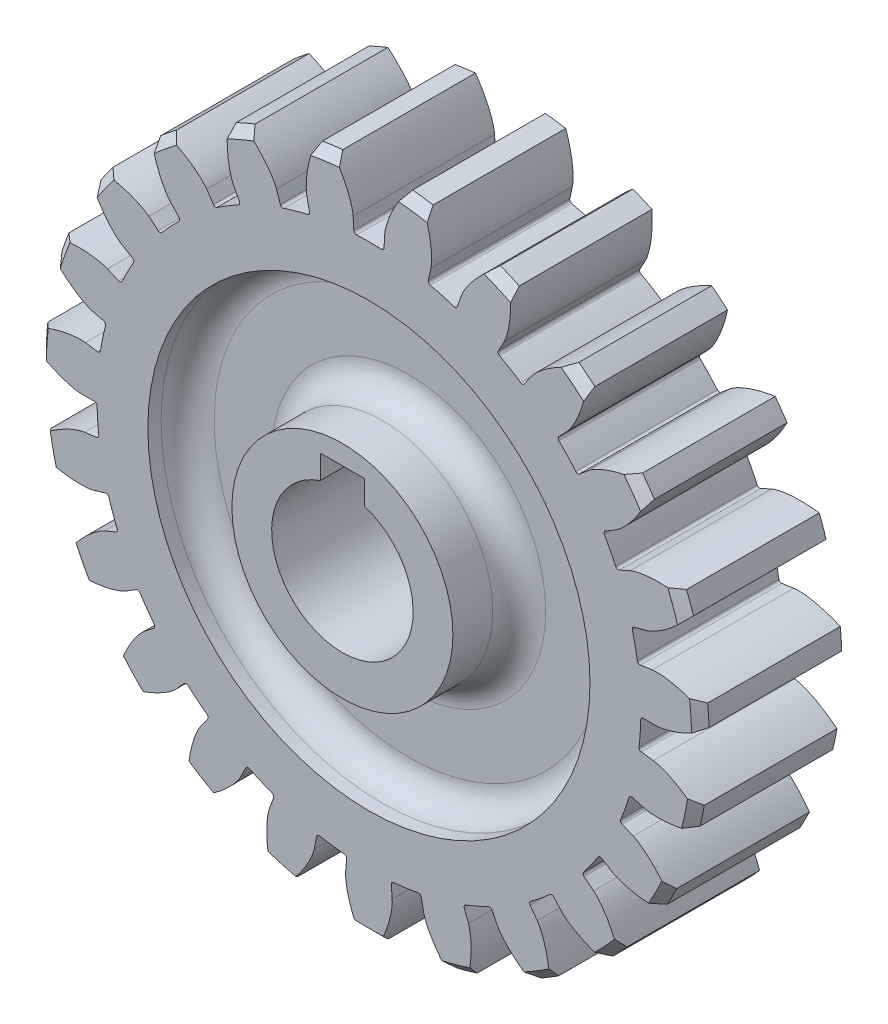
SolidWorks part; units mm, degrees
ref_plane "中间平面" through (0, 0, 0) normal (0, 0, 1) x (1, 0, 0)
ref_plane "上视基准面" through (0, 0, 0) normal (0, 1, 0) x (1, 0, 0)
ref_plane "右视基准面" through (0, 0, 0) normal (1, 0, 0) x (0, 0, -1)
sketch "直齿轮" plane through (0, 0, 0) normal (0, 0, 1) x (1, 0, 0)
  line L0 (0, 0) -> (-2.3544, 34.4196) construction
  line L2 (-1.787, 32.3701) -> (0, 0)
  line L3 (0, 0) -> (0, 52) construction
  line L4 (2.3544, 34.4196) -> (0, 0) construction
  line L6 (0, 0) -> (1.787, 32.3701)
  circle A0 centre (0, 0) radius 32.4194
  circle A1 centre (0, 0) radius 30.75
  arc A2 (2.3544, 34.4196) -> (-2.3544, 34.4196) centre (0, 0) ccw
  circle A3 centre (0, 0) radius 37.5
  spline S0 degree 4 poles (-1.787, 32.3701) (-1.7887, 32.4009) (-1.7934, 32.4623) (-1.8081, 32.5848) (-1.8484, 32.8281) (-1.9198, 33.1474) (-2.0304, 33.5397) (-2.2127, 34.0782) (-2.4377, 34.6365) (-2.7111, 35.2233) (-3.1079, 35.9742) (-3.8554, 37.2208) (-5.1552, 38.9723) (-7.4145, 41.3347) (-10.7378, 43.9018) (-14.7558, 46.1681) (-19.3803, 47.9889) (-24.1918, 49.2236) (-29.1102, 49.907) (-34.3171, 50.0805) (-40.7527, 49.6222) (-48.3054, 48.0952) (-56.7314, 45.058) (-64.3662, 40.876) (-70.4218, 36.5402) (-76.0488, 31.6736) (-80.363, 27.2133) (-84.2805, 22.4024) (-87.7873, 17.291) (-90.3418, 13.0408) (-93.2175, 7.5498) (-96.156, 0.7112) (-98.2587, -5.7849) (-99.6885, -11.8176) (-100.4666, -16.0841) (-100.8478, -18.5329) (-101.166, -20.9904) (-101.3894, -23.1477) (-101.5419, -24.9995) (-101.6431, -26.5457) (-101.7087, -27.7814) (-101.7587, -29.0225) (-101.7936, -30.2555) (-101.811, -31.3931) (-101.8163, -32.3958) (-101.8115, -33.3287) (-101.803, -34.0741) (-101.7825, -35.0407) (-101.7621, -35.7456) (-101.7112, -37.1392) (-101.6516, -38.2432) (-101.5692, -39.582) (-101.4747, -40.777) (-101.3876, -41.8018) (-101.2922, -42.7795) (-101.1864, -43.7836) (-101.0428, -45.0197) (-100.8513, -46.5113) (-100.6365, -47.9927) (-100.3982, -49.4757) (-100.227, -50.4595) (-100.1383, -50.9523) (-100.0932, -51.1978) knots 0 0 0 0 0 0.000701 0.001401 0.002802 0.005604 0.008133 0.010661 0.015718 0.019279 0.022839 0.02996 0.048734 0.068727 0.096889 0.125051 0.153212 0.181374 0.209535 0.237696 0.271429 0.327752 0.384075 0.440398 0.46856 0.496721 0.553044 0.581206 0.609367 0.637529 0.66569 0.722013 0.778336 0.792417 0.806497 0.820578 0.834659 0.84874 0.85578 0.86282 0.869861 0.876901 0.883942 0.890982 0.895509 0.900036 0.904564 0.909091 0.914773 0.920455 0.931818 0.9375 0.943182 0.948864 0.954545 0.960227 0.965909 0.977273 0.988636 0.994318 1 1 1 1 1 construction
  spline S1 degree 4 poles (-1.787, 32.3701) (-1.7887, 32.4009) (-1.7934, 32.4623) (-1.8081, 32.5848) (-1.8484, 32.8281) (-1.9198, 33.1474) (-2.0304, 33.5397) (-2.2127, 34.0782) (-2.4377, 34.6365) (-2.7111, 35.2233) (-3.1079, 35.9742) (-3.8554, 37.2208) (-5.1552, 38.9723) (-7.4145, 41.3347) (-10.7378, 43.9018) (-14.7558, 46.1681) (-19.3803, 47.9889) (-24.1918, 49.2236) (-29.1102, 49.907) (-34.3171, 50.0805) (-40.7527, 49.6222) (-48.3054, 48.0952) (-56.7314, 45.058) (-64.3662, 40.876) (-70.4218, 36.5402) (-76.0488, 31.6736) (-80.363, 27.2133) (-84.2805, 22.4024) (-87.7873, 17.291) (-90.3418, 13.0408) (-93.2175, 7.5498) (-96.156, 0.7112) (-98.2587, -5.7849) (-99.6885, -11.8176) (-100.4666, -16.0841) (-100.8478, -18.5329) (-101.166, -20.9904) (-101.3894, -23.1477) (-101.5419, -24.9995) (-101.6431, -26.5457) (-101.7087, -27.7814) (-101.7587, -29.0225) (-101.7936, -30.2555) (-101.811, -31.3931) (-101.8163, -32.3958) (-101.8115, -33.3287) (-101.803, -34.0741) (-101.7885, -34.7556) (-101.7793, -35.1229) (-101.7742, -35.3039) knots 0 0 0 0 0 0.000701 0.001401 0.002802 0.005604 0.008133 0.010661 0.015718 0.019279 0.022839 0.02996 0.048734 0.068727 0.096889 0.125051 0.153212 0.181374 0.209535 0.237696 0.271429 0.327752 0.384075 0.440398 0.46856 0.496721 0.553044 0.581206 0.609367 0.637529 0.66569 0.722013 0.778336 0.792417 0.806497 0.820578 0.834659 0.84874 0.85578 0.86282 0.869861 0.876901 0.883942 0.890982 0.895509 0.900036 0.904564 0.909091 0.909091 0.909091 0.909091 0.909091
  spline S2 degree 4 poles (1.787, 32.3701) (1.7887, 32.4009) (1.7934, 32.4623) (1.8081, 32.5848) (1.8484, 32.8281) (1.9198, 33.1474) (2.0304, 33.5397) (2.2127, 34.0782) (2.4377, 34.6365) (2.7111, 35.2233) (3.1079, 35.9742) (3.8554, 37.2208) (5.1552, 38.9723) (7.4145, 41.3347) (10.7378, 43.9018) (14.7558, 46.1681) (19.3803, 47.9889) (24.1918, 49.2236) (29.1102, 49.907) (34.3171, 50.0805) (40.7527, 49.6222) (48.3054, 48.0952) (56.7314, 45.058) (64.3662, 40.876) (70.4218, 36.5402) (76.0488, 31.6736) (80.363, 27.2133) (84.2805, 22.4024) (87.7873, 17.291) (90.3418, 13.0408) (93.2175, 7.5498) (96.156, 0.7112) (98.2587, -5.7849) (99.6885, -11.8176) (100.4666, -16.0841) (100.8478, -18.5329) (101.166, -20.9904) (101.3894, -23.1477) (101.5419, -24.9995) (101.6431, -26.5457) (101.7087, -27.7814) (101.7587, -29.0225) (101.7936, -30.2555) (101.811, -31.3931) (101.8163, -32.3958) (101.8115, -33.3287) (101.803, -34.0741) (101.7825, -35.0407) (101.7621, -35.7456) (101.7112, -37.1392) (101.6516, -38.2432) (101.5692, -39.582) (101.4747, -40.777) (101.3876, -41.8018) (101.2922, -42.7795) (101.1864, -43.7836) (101.0428, -45.0197) (100.8513, -46.5113) (100.6365, -47.9927) (100.3982, -49.4757) (100.227, -50.4595) (100.1383, -50.9523) (100.0932, -51.1978) knots 0 0 0 0 0 0.000701 0.001401 0.002802 0.005604 0.008133 0.010661 0.015718 0.019279 0.022839 0.02996 0.048734 0.068727 0.096889 0.125051 0.153212 0.181374 0.209535 0.237696 0.271429 0.327752 0.384075 0.440398 0.46856 0.496721 0.553044 0.581206 0.609367 0.637529 0.66569 0.722013 0.778336 0.792417 0.806497 0.820578 0.834659 0.84874 0.85578 0.86282 0.869861 0.876901 0.883942 0.890982 0.895509 0.900036 0.904564 0.909091 0.914773 0.920455 0.931818 0.9375 0.943182 0.948864 0.954545 0.960227 0.965909 0.977273 0.988636 0.994318 1 1 1 1 1 construction
  spline S3 degree 4 poles (1.787, 32.3701) (1.7887, 32.4009) (1.7934, 32.4623) (1.8081, 32.5848) (1.8484, 32.8281) (1.9198, 33.1474) (2.0304, 33.5397) (2.2127, 34.0782) (2.4377, 34.6365) (2.7111, 35.2233) (3.1079, 35.9742) (3.8554, 37.2208) (5.1552, 38.9723) (7.4145, 41.3347) (10.7378, 43.9018) (14.7558, 46.1681) (19.3803, 47.9889) (24.1918, 49.2236) (29.1102, 49.907) (34.3171, 50.0805) (40.7527, 49.6222) (48.3054, 48.0952) (56.7314, 45.058) (64.3662, 40.876) (70.4218, 36.5402) (76.0488, 31.6736) (80.363, 27.2133) (84.2805, 22.4024) (87.7873, 17.291) (90.3418, 13.0408) (93.2175, 7.5498) (96.156, 0.7112) (98.2587, -5.7849) (99.6885, -11.8176) (100.4666, -16.0841) (100.8478, -18.5329) (101.166, -20.9904) (101.3894, -23.1477) (101.5419, -24.9995) (101.6431, -26.5457) (101.7087, -27.7814) (101.7587, -29.0225) (101.7936, -30.2555) (101.811, -31.3931) (101.8163, -32.3958) (101.8115, -33.3287) (101.803, -34.0741) (101.7885, -34.7556) (101.7793, -35.1229) (101.7742, -35.3039) knots 0 0 0 0 0 0.000701 0.001401 0.002802 0.005604 0.008133 0.010661 0.015718 0.019279 0.022839 0.02996 0.048734 0.068727 0.096889 0.125051 0.153212 0.181374 0.209535 0.237696 0.271429 0.327752 0.384075 0.440398 0.46856 0.496721 0.553044 0.581206 0.609367 0.637529 0.66569 0.722013 0.778336 0.792417 0.806497 0.820578 0.834659 0.84874 0.85578 0.86282 0.869861 0.876901 0.883942 0.890982 0.895509 0.900036 0.904564 0.909091 0.909091 0.909091 0.909091 0.909091
  dimension "基圆直径" = 64.8388
  dimension "齿根圆" = 61.5
  dimension "分度圆" = 69
  dimension "齿顶圆" = 75
  dimension "D1" = 4.7124
sketch "圆" plane through (0, 0, 0) normal (0, 0, 1) x (1, 0, 0)
  circle A0 centre (0, 0) radius 37.5 construction
  circle A1 centre (0, 0) radius 37.5
extrude "毛胚" add sketch "圆" along normal mid plane 16
chamfer "轮齿倒角" distance 1 angle 45 1 edges at (37.5, 0, 8)
sketch "齿形" plane through (0, 0, 0) normal (0, 0, 1) x (1, 0, 0)
  line L4 (0, 0) -> (1.787, 32.3701) construction
  line L5 (-1.787, 32.3701) -> (0, 0) construction
  line L6 (0, 0) -> (1.787, 32.3701)
  line L7 (-1.787, 32.3701) -> (0, 0)
  circle A4 centre (0, 0) radius 30.75 construction
  circle A5 centre (0, 0) radius 37.5 construction
  circle A6 centre (0, 0) radius 30.75
  circle A7 centre (0, 0) radius 37.5
  spline S1 degree 4 poles (-997.5323, 54.0492) (25.4941, 26.9163) (2.2443, 29.3408) (1.5615, 31.092) (1.8484, 32.8281) (1.9198, 33.1474) (2.0304, 33.5397) (2.2127, 34.0782) (2.4377, 34.6365) (2.7111, 35.2233) (3.1079, 35.9742) (3.8554, 37.2208) (5.1552, 38.9723) (7.4145, 41.3347) (10.7378, 43.9018) (14.7558, 46.1681) (19.3803, 47.9889) (24.1918, 49.2236) (29.1102, 49.907) (34.3171, 50.0805) (40.7527, 49.6222) (48.3054, 48.0952) (56.7314, 45.058) (64.3662, 40.876) (70.4218, 36.5402) (76.0488, 31.6736) (80.363, 27.2133) (84.2805, 22.4024) (87.7873, 17.291) (90.3418, 13.0408) (93.2175, 7.5498) (96.156, 0.7112) (98.2587, -5.7849) (99.6885, -11.8176) (100.4666, -16.0841) (100.8478, -18.5329) (101.166, -20.9904) (101.3894, -23.1477) (101.5419, -24.9995) (101.6431, -26.5457) (101.7087, -27.7814) (101.7587, -29.0225) (101.7936, -30.2555) (101.811, -31.3931) (101.8163, -32.3958) (101.8115, -33.3287) (101.777, -36.37) (101.5324, -42.4213) (102.5811, 1.12) (73.2196, -1034.8438) knots -0.034379 -0.034379 -0.034379 -0.034379 -0.034379 0.000701 0.001401 0.002802 0.005604 0.008133 0.010661 0.015718 0.019279 0.022839 0.02996 0.048734 0.068727 0.096889 0.125051 0.153212 0.181374 0.209535 0.237696 0.271429 0.327752 0.384075 0.440398 0.46856 0.496721 0.553044 0.581206 0.609367 0.637529 0.66569 0.722013 0.778336 0.792417 0.806497 0.820578 0.834659 0.84874 0.85578 0.86282 0.869861 0.876901 0.883942 0.890982 0.895509 0.900036 0.904564 0.964873 0.964873 0.964873 0.964873 0.964873 only from (1.787, 32.3701) to (101.7742, -35.3039) construction
  spline S3 degree 4 poles (997.5323, 54.0492) (-25.4941, 26.9163) (-2.2443, 29.3408) (-1.5615, 31.092) (-1.8484, 32.8281) (-1.9198, 33.1474) (-2.0304, 33.5397) (-2.2127, 34.0782) (-2.4377, 34.6365) (-2.7111, 35.2233) (-3.1079, 35.9742) (-3.8554, 37.2208) (-5.1552, 38.9723) (-7.4145, 41.3347) (-10.7378, 43.9018) (-14.7558, 46.1681) (-19.3803, 47.9889) (-24.1918, 49.2236) (-29.1102, 49.907) (-34.3171, 50.0805) (-40.7527, 49.6222) (-48.3054, 48.0952) (-56.7314, 45.058) (-64.3662, 40.876) (-70.4218, 36.5402) (-76.0488, 31.6736) (-80.363, 27.2133) (-84.2805, 22.4024) (-87.7873, 17.291) (-90.3418, 13.0408) (-93.2175, 7.5498) (-96.156, 0.7112) (-98.2587, -5.7849) (-99.6885, -11.8176) (-100.4666, -16.0841) (-100.8478, -18.5329) (-101.166, -20.9904) (-101.3894, -23.1477) (-101.5419, -24.9995) (-101.6431, -26.5457) (-101.7087, -27.7814) (-101.7587, -29.0225) (-101.7936, -30.2555) (-101.811, -31.3931) (-101.8163, -32.3958) (-101.8115, -33.3287) (-101.777, -36.37) (-101.5324, -42.4213) (-102.5811, 1.12) (-73.2196, -1034.8438) knots -0.034379 -0.034379 -0.034379 -0.034379 -0.034379 0.000701 0.001401 0.002802 0.005604 0.008133 0.010661 0.015718 0.019279 0.022839 0.02996 0.048734 0.068727 0.096889 0.125051 0.153212 0.181374 0.209535 0.237696 0.271429 0.327752 0.384075 0.440398 0.46856 0.496721 0.553044 0.581206 0.609367 0.637529 0.66569 0.722013 0.778336 0.792417 0.806497 0.820578 0.834659 0.84874 0.85578 0.86282 0.869861 0.876901 0.883942 0.890982 0.895509 0.900036 0.904564 0.964873 0.964873 0.964873 0.964873 0.964873 only from (-1.787, 32.3701) to (-101.7742, -35.3039) construction
  spline S4 degree 4 poles (1.787, 32.3701) (1.7887, 32.4009) (1.7934, 32.4623) (1.8081, 32.5848) (1.8484, 32.8281) (1.9198, 33.1474) (2.0304, 33.5397) (2.2127, 34.0782) (2.4377, 34.6365) (2.7111, 35.2233) (3.1079, 35.9742) (3.8554, 37.2208) (5.1552, 38.9723) (7.4145, 41.3347) (10.7378, 43.9018) (14.7558, 46.1681) (19.3803, 47.9889) (24.1918, 49.2236) (29.1102, 49.907) (34.3171, 50.0805) (40.7527, 49.6222) (48.3054, 48.0952) (56.7314, 45.058) (64.3662, 40.876) (70.4218, 36.5402) (76.0488, 31.6736) (80.363, 27.2133) (84.2805, 22.4024) (87.7873, 17.291) (90.3418, 13.0408) (93.2175, 7.5498) (96.156, 0.7112) (98.2587, -5.7849) (99.6885, -11.8176) (100.4666, -16.0841) (100.8478, -18.5329) (101.166, -20.9904) (101.3894, -23.1477) (101.5419, -24.9995) (101.6431, -26.5457) (101.7087, -27.7814) (101.7587, -29.0225) (101.7936, -30.2555) (101.811, -31.3931) (101.8163, -32.3958) (101.8115, -33.3287) (101.803, -34.0741) (101.7885, -34.7556) (101.7793, -35.1229) (101.7742, -35.3039) knots 0 0 0 0 0 0.000701 0.001401 0.002802 0.005604 0.008133 0.010661 0.015718 0.019279 0.022839 0.02996 0.048734 0.068727 0.096889 0.125051 0.153212 0.181374 0.209535 0.237696 0.271429 0.327752 0.384075 0.440398 0.46856 0.496721 0.553044 0.581206 0.609367 0.637529 0.66569 0.722013 0.778336 0.792417 0.806497 0.820578 0.834659 0.84874 0.85578 0.86282 0.869861 0.876901 0.883942 0.890982 0.895509 0.900036 0.904564 0.909091 0.909091 0.909091 0.909091 0.909091
  spline S5 degree 4 poles (-1.787, 32.3701) (-1.7887, 32.4009) (-1.7934, 32.4623) (-1.8081, 32.5848) (-1.8484, 32.8281) (-1.9198, 33.1474) (-2.0304, 33.5397) (-2.2127, 34.0782) (-2.4377, 34.6365) (-2.7111, 35.2233) (-3.1079, 35.9742) (-3.8554, 37.2208) (-5.1552, 38.9723) (-7.4145, 41.3347) (-10.7378, 43.9018) (-14.7558, 46.1681) (-19.3803, 47.9889) (-24.1918, 49.2236) (-29.1102, 49.907) (-34.3171, 50.0805) (-40.7527, 49.6222) (-48.3054, 48.0952) (-56.7314, 45.058) (-64.3662, 40.876) (-70.4218, 36.5402) (-76.0488, 31.6736) (-80.363, 27.2133) (-84.2805, 22.4024) (-87.7873, 17.291) (-90.3418, 13.0408) (-93.2175, 7.5498) (-96.156, 0.7112) (-98.2587, -5.7849) (-99.6885, -11.8176) (-100.4666, -16.0841) (-100.8478, -18.5329) (-101.166, -20.9904) (-101.3894, -23.1477) (-101.5419, -24.9995) (-101.6431, -26.5457) (-101.7087, -27.7814) (-101.7587, -29.0225) (-101.7936, -30.2555) (-101.811, -31.3931) (-101.8163, -32.3958) (-101.8115, -33.3287) (-101.803, -34.0741) (-101.7885, -34.7556) (-101.7793, -35.1229) (-101.7742, -35.3039) knots 0 0 0 0 0 0.000701 0.001401 0.002802 0.005604 0.008133 0.010661 0.015718 0.019279 0.022839 0.02996 0.048734 0.068727 0.096889 0.125051 0.153212 0.181374 0.209535 0.237696 0.271429 0.327752 0.384075 0.440398 0.46856 0.496721 0.553044 0.581206 0.609367 0.637529 0.66569 0.722013 0.778336 0.792417 0.806497 0.820578 0.834659 0.84874 0.85578 0.86282 0.869861 0.876901 0.883942 0.890982 0.895509 0.900036 0.904564 0.909091 0.909091 0.909091 0.909091 0.909091
extrude "插齿" cut sketch "齿形" against normal mid plane 16 contours S5 A6 S4 A7 region at (0, 34.6185, 0)
fillet "圆角1" [suppressed] radius 0.3
pattern_circular "圆周阵列1" [suppressed] count 23 over 360 of bodies 165
fillet "圆角2" radius 0.3 2 edges at (1.695, 30.7032, 0) (-1.695, 30.7032, 0)
pattern_circular "圆周阵列2" count 23 over 360 about axis through (0, 0, 8) along (0, 0, -1) of "圆角2", "插齿"
sketch "分度圆" plane through (0, 0, 0) normal (0, 0, 1) x (1, 0, 0)
  circle A0 centre (0, 0) radius 34.5 construction
  circle A1 centre (0, 0) radius 34.5 construction
sketch "草图1" plane through (0, 0, 8) normal (0, 0, 1) x (1, 0, 0)
  circle A1 centre (0, 0) radius 12.5
  dimension "D1" = 25
extrude "凸台-拉伸1" add sketch "草图1" against normal blind 20 from offset 3
sketch "草图2" plane through (0, 0, 11) normal (0, 0, 1) x (1, 0, 0)
  line L0 (2.5, 5.7) -> (2.5, 7.5993) construction
  line L1 (-2.5, 5.7) -> (2.5, 5.7) construction
  line L2 (-2.5, 7.5993) -> (-2.5, 10.3)
  line L3 (-2.5, 10.3) -> (2.5, 10.3)
  line L4 (2.5, 7.5993) -> (2.5, 10.3)
  line L5 (-2.5, 5.7) -> (2.5, 10.3) construction
  line L6 (-2.5, 10.3) -> (2.5, 5.7) construction
  line L7 (-2.5, 5.7) -> (-2.5, 7.5993) construction
  arc A0 (-2.5, 7.5993) -> (2.5, 7.5993) centre (0, 0) ccw
  arc A1 (0, 8) -> (-2.5, 7.5993) centre (0, 0) ccw construction
  arc A2 (2.5, 7.5993) -> (0, 8) centre (0, 0) ccw construction
  point P3 (0, 8)
  dimension "D1" = 16
  dimension "D2" = 18.3
  dimension "D3" = 5
extrude "切除-拉伸1" cut sketch "草图2" against normal through all
sketch "草图3" plane through (0, 0, 8) normal (0, 0, 1) x (1, 0, 0)
  circle A0 centre (0, 0) radius 25
  circle A1 centre (0, 0) radius 12.5 construction
  circle A2 centre (0, 0) radius 12.5
  dimension "D1" = 50
extrude "切除-拉伸2" cut sketch "草图3" against normal blind 4.5
fillet "圆角3" radius 3 2 edges at (25, 0, 3.5) (12.5, 0, 3.5)
mirror "镜向1" about plane through (0, 0, 0) normal (0, 0, 1) of "切除-拉伸2", "圆角3"
equation "\"m\" = 3'模数"
equation "\"z\" = 23'齿数"
equation "\"a\"= 20'压力角（常见为20°）"
equation "\"B\" = 16'齿宽"
equation "\"C1\"= 1'轮齿倒角（若设为0，则无倒角）"
equation "\"x\"= 0'变位系数（不懂勿动）"
equation "\"ha\"= 1'齿顶高系数（不懂勿动）"
equation "\"c\"= 0.25'顶隙系数（不懂勿动）"
equation "\"基圆直径@直齿轮\"= \"m\" * \"z\" * cos ( \"a\" )"
equation "\"齿根圆@直齿轮\" = \"m\" * ( \"z\" - 2 * ( \"ha\" - \"x\" + \"c\" ) )"
equation "\"分度圆@直齿轮\"=\"m\" * \"z\""
equation "\"齿顶圆@直齿轮\" = \"m\" * ( \"z\" + 2 * ( \"ha\" + \"x\" ) )"
equation "\"R\"= 0.3'齿根圆角"
equation "\"D1\"= \"R\""
equation "\"D1@毛胚\" = \"B\""
equation "\"D1@轮齿倒角\" = IIF ( \"C1\" > 0 , \"C1\" , 0.001 )"
equation "\"轮齿倒角\"= IIF ( \"C1\" > 0 , \"unsuppressed\" , \"suppressed\" )"
equation "\"D1@插齿\" = \"B\""
equation "\"D1@圆周阵列1\" = \"z\""
equation "\"D1@直齿轮\"= \"m\" * ( pi / 2 ) - 2 * \"m\" * tan ( \"a\" ) * \"x\"'作者：机械菌-"
equation "\"D1@圆角1\"=\"R\""
equation "\"圆角1\" = IIF ( \"m\" * ( \"z\" - 2 * ( \"ha\" - \"x\" + \"c\" ) ) > \"m\" * \"z\" * cos ( \"a\" ) , \"unsuppressed\" , \"suppressed\" )"
equation "\"圆周阵列1\"= IIF ( \"m\" * ( \"z\" - 2 * ( \"ha\" - \"x\" + \"c\" ) ) > \"m\" * \"z\" * cos ( \"a\" ) , \"unsuppressed\" , \"suppressed\" )"
equation "\"D1@圆角2\"=\"R\""
equation "\"D1@圆周阵列2\" = \"z\""
equation "\"圆角2\" = IIF ( \"m\" * ( \"z\" - 2 * ( \"ha\" - \"x\" + \"c\" ) ) < \"m\" * \"z\" * cos ( \"a\" ) , \"unsuppressed\" , \"suppressed\" )"
equation "\"圆周阵列2\"= IIF ( \"m\" *  ( \"z\" - 2 *  ( \"ha\" - \"x\" + \"c\" )  )  < \"m\" * \"z\" * cos ( \"a\" )  ,  unsuppressed  ,  suppressed  ) "
